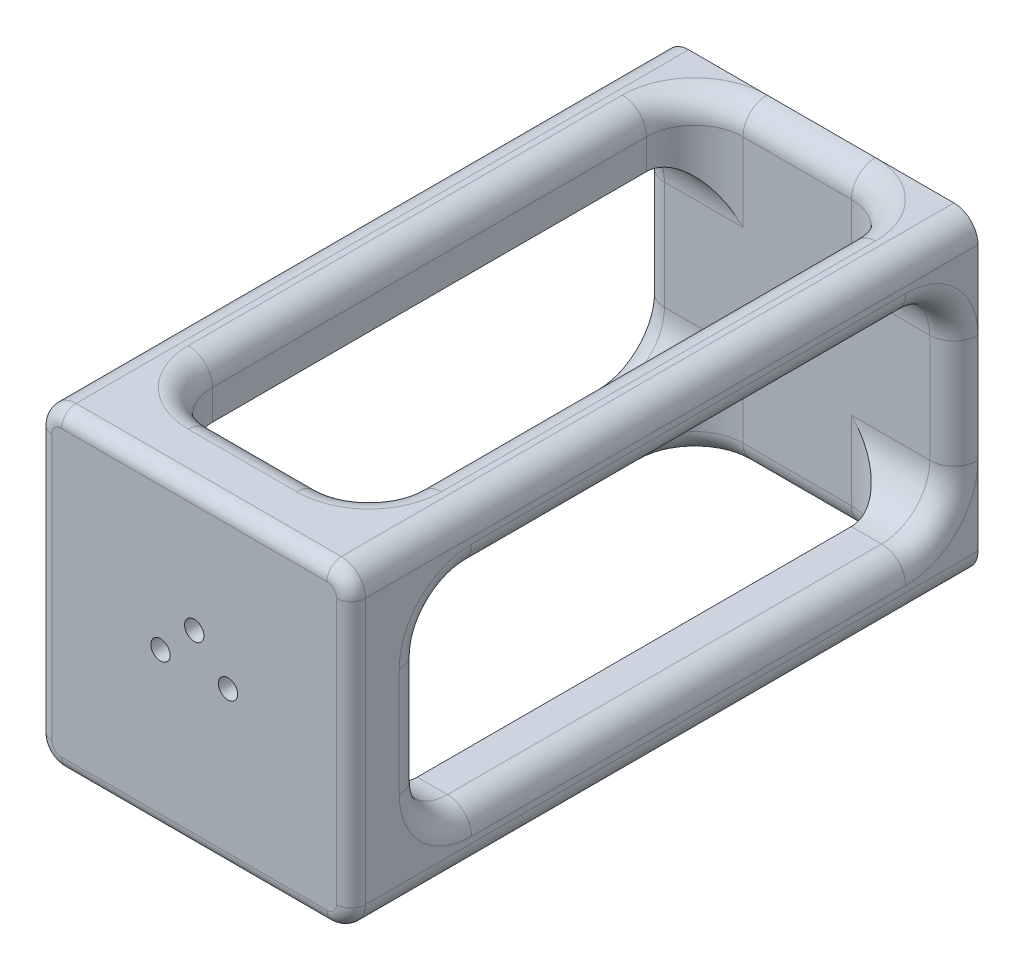
SolidWorks part; units mm, degrees
ref_plane "前视基准面" through (0, 0, 0) normal (0, 0, 1) x (1, 0, 0)
ref_plane "上视基准面" through (0, 0, 0) normal (0, 1, 0) x (1, 0, 0)
ref_plane "右视基准面" through (0, 0, 0) normal (1, 0, 0) x (0, 0, -1)
other "Configuration Table"
sketch "草图1" plane through (0, 0, 0) normal (0, 0, 1) x (1, 0, 0)
  line L0 (0, 0) -> (0, 45533.1781) construction
  line L1 (0, 0) -> (45533.1781, 0) construction
  line L3 (-32.5, 32.5) -> (32.5, 32.5)
  line L4 (-32.5, 32.5) -> (-32.5, -32.5)
  line L5 (-32.5, -32.5) -> (32.5, -32.5)
  line L6 (32.5, 32.5) -> (32.5, -32.5)
  line L7 (-32.5, 32.5) -> (32.5, -32.5) construction
  line L8 (-32.5, -32.5) -> (32.5, 32.5) construction
  circle A0 centre (-26.87, 26.87) radius 2.15
  circle A1 centre (26.87, 26.87) radius 2.15
  circle A2 centre (26.87, -26.87) radius 2.15
  circle A3 centre (-26.87, -26.87) radius 2.15
  point P5 (0, 0)
  dimension "D3" = 53.74
  dimension "D4" = 4.3
  dimension "D1" = 65
  dimension "D2" = 65
extrude "凸台-拉伸1" add sketch "草图1" along normal blind 5
sketch "草图3" plane through (0, 0, 5) normal (0, 0, 1) x (1, 0, 0)
  line L0 (0, 0) -> (0, 50000) construction
  line L1 (0, 0) -> (50000, 0) construction
  line L2 (21.24, 32.5) -> (32.5, 21.24) construction
  line L3 (-21.24, 21.24) -> (-32.5, 21.24)
  line L4 (-21.24, 21.24) -> (-21.24, 32.5)
  line L5 (-21.24, 32.5) -> (-32.5, 32.5)
  line L6 (-32.5, 21.24) -> (-32.5, 32.5)
  line L7 (-21.24, 21.24) -> (-32.5, 32.5) construction
  line L8 (-21.24, 32.5) -> (-32.5, 21.24) construction
  line L9 (21.24, 21.24) -> (32.5, 32.5) construction
  line L10 (32.5, 21.24) -> (32.5, 32.5)
  line L11 (21.24, 32.5) -> (32.5, 32.5)
  line L12 (21.24, 21.24) -> (21.24, 32.5)
  line L13 (21.24, 21.24) -> (32.5, 21.24)
  line L14 (21.24, -21.24) -> (32.5, -32.5) construction
  line L15 (-21.24, -32.5) -> (-32.5, -21.24) construction
  line L16 (-21.24, -21.24) -> (-32.5, -32.5) construction
  line L17 (21.24, -32.5) -> (32.5, -21.24) construction
  line L18 (21.24, -21.24) -> (32.5, -21.24)
  line L19 (21.24, -21.24) -> (21.24, -32.5)
  line L20 (21.24, -32.5) -> (32.5, -32.5)
  line L21 (32.5, -21.24) -> (32.5, -32.5)
  line L22 (-32.5, -21.24) -> (-32.5, -32.5)
  line L23 (-21.24, -32.5) -> (-32.5, -32.5)
  line L24 (-21.24, -21.24) -> (-21.24, -32.5)
  line L25 (-21.24, -21.24) -> (-32.5, -21.24)
  point P5 (-26.87, 26.87)
  point P16 (26.87, 26.87)
  point P25 (26.87, -26.87)
  point P26 (-26.87, -26.87)
extrude "凸台-拉伸2" add sketch "草图3" along normal blind 120
sketch "草图4" plane through (0, 0, 125) normal (0, 0, 1) x (1, 0, 0)
  line L0 (0, 0) -> (50000, 0) construction
  line L1 (-32.5, 32.5) -> (32.5, 32.5)
  line L2 (-32.5, 32.5) -> (-32.5, -32.5)
  line L3 (-32.5, -32.5) -> (32.5, -32.5)
  line L4 (32.5, 32.5) -> (32.5, -32.5)
  line L5 (0, 0) -> (0, 50000) construction
  circle A0 centre (0, 0) radius 7 construction
  circle A1 centre (0, 7) radius 2
  circle A2 centre (7, 0) radius 2
  circle A3 centre (-7, 0) radius 2
  dimension "D1" = 14
  dimension "D2" = 4
  dimension "D3" = 4
  dimension "D4" = 4
extrude "凸台-拉伸3" add sketch "草图4" along normal blind 5
fillet "圆角1" radius 10 8 edges at (-26.87, -21.24, 5) (-21.24, -26.87, 5) (-21.24, 26.87, 5) (-26.87, 21.24, 5) (21.24, 26.87, 5) (26.87, 21.24, 5) (21.24, -26.87, 5) (26.87, -21.24, 5)
fillet "圆角5" radius 3 4 edges at (32.5, 0, 130) (0, 32.5, 130) (-32.5, 0, 130) (0, -32.5, 130)
sketch "草图6" plane through (0, 0, 125) normal (0, 0, -1) x (-1, 0, 0)
  line L12 (32.5, 21.24) -> (21.24, 21.24)
  line L13 (21.24, 21.24) -> (21.24, 32.5)
  line L14 (21.24, 32.5) -> (-21.24, 32.5)
  line L15 (-21.24, 32.5) -> (-21.24, 21.24)
  line L16 (-21.24, 21.24) -> (-32.5, 21.24)
  line L17 (-32.5, 21.24) -> (-32.5, -21.24)
  line L18 (-32.5, -21.24) -> (-21.24, -21.24)
  line L19 (-21.24, -21.24) -> (-21.24, -32.5)
  line L20 (-21.24, -32.5) -> (21.24, -32.5)
  line L21 (21.24, -32.5) -> (21.24, -21.24)
  line L22 (21.24, -21.24) -> (32.5, -21.24)
  line L23 (32.5, -21.24) -> (32.5, 21.24)
  line L24 (32.5, 21.24) -> (21.24, 21.24)
  line L25 (21.24, 21.24) -> (21.24, 32.5)
  line L26 (21.24, 32.5) -> (-21.24, 32.5)
  line L27 (-21.24, 32.5) -> (-21.24, 21.24)
  line L28 (-21.24, 21.24) -> (-32.5, 21.24)
  line L29 (-32.5, 21.24) -> (-32.5, -21.24)
  line L30 (-32.5, -21.24) -> (-21.24, -21.24)
  line L31 (-21.24, -21.24) -> (-21.24, -32.5)
  line L32 (-21.24, -32.5) -> (21.24, -32.5)
  line L33 (21.24, -32.5) -> (21.24, -21.24)
  line L34 (21.24, -21.24) -> (32.5, -21.24)
  line L35 (32.5, -21.24) -> (32.5, 21.24)
  dimension "D1" = 0
extrude "凸台-拉伸4" add sketch "草图6" along normal blind 10
fillet "圆角6" radius 10 8 edges at (-26.87, -21.24, 115) (-21.24, -26.87, 115) (26.87, -21.24, 115) (21.24, -26.87, 115) (-26.87, 21.24, 115) (-21.24, 26.87, 115) (26.87, 21.24, 115) (21.24, 26.87, 115)
fillet "圆角8" radius 5 8 edges at (-18.3111, 32.5, 112.0711) (18.3111, 32.5, 112.0711) (18.3111, 32.5, 7.9289) (-18.3111, 32.5, 7.9289) (0, 32.5, 5) (21.24, 32.5, 60) (0, 32.5, 115) (-21.24, 32.5, 60)
fillet "圆角9" radius 5 8 edges at (32.5, 18.3111, 112.0711) (32.5, -18.3111, 112.0711) (32.5, -18.3111, 7.9289) (32.5, 18.3111, 7.9289) (32.5, -21.24, 60) (32.5, 0, 5) (32.5, 0, 115) (32.5, 21.24, 60)
fillet "圆角10" radius 5 8 edges at (18.3111, -32.5, 112.0711) (-18.3111, -32.5, 112.0711) (-18.3111, -32.5, 7.9289) (18.3111, -32.5, 7.9289) (-21.24, -32.5, 60) (0, -32.5, 5) (0, -32.5, 115) (21.24, -32.5, 60)
fillet "圆角11" radius 5 8 edges at (-32.5, -18.3111, 112.0711) (-32.5, 18.3111, 112.0711) (-32.5, 18.3111, 7.9289) (-32.5, -18.3111, 7.9289) (-32.5, 21.24, 60) (-32.5, 0, 5) (-32.5, 0, 115) (-32.5, -21.24, 60)
fillet "圆角12" radius 5 8 edges at (-31.6213, 31.6213, 129.1213) (31.6213, 31.6213, 129.1213) (31.6213, -31.6213, 129.1213) (-31.6213, -31.6213, 129.1213) (-32.5, -32.5, 63.5) (32.5, -32.5, 63.5) (32.5, 32.5, 63.5) (-32.5, 32.5, 63.5)
